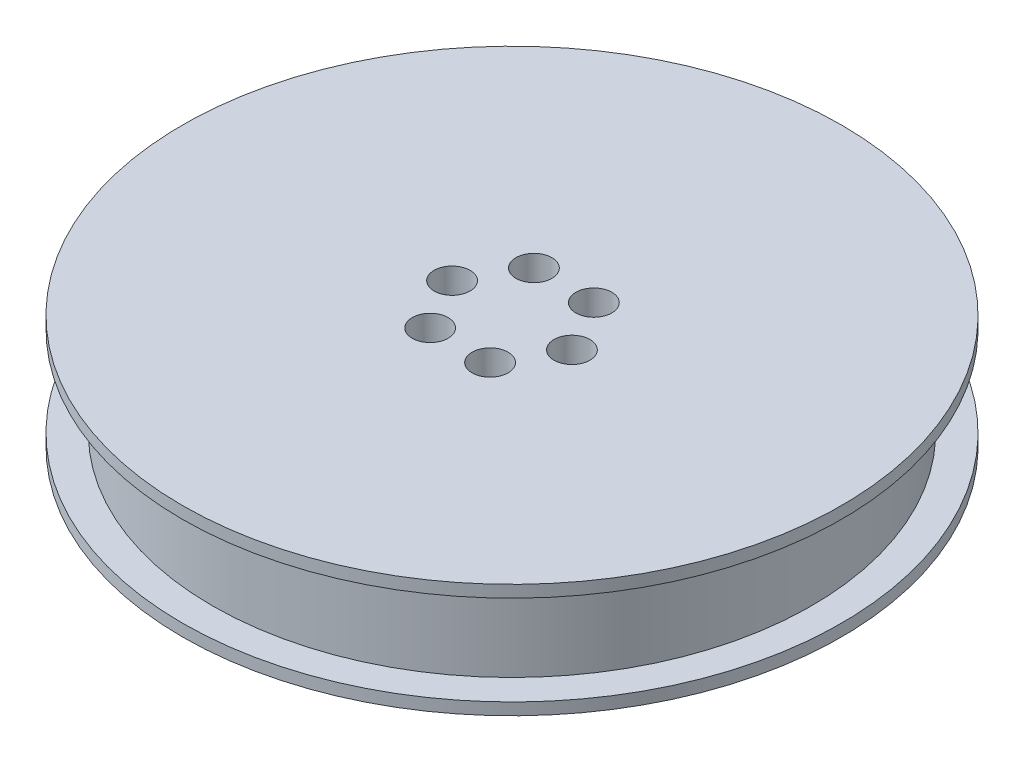
SolidWorks part; units mm, degrees
material "PETG"
ref_plane "Front Plane" through (0, 0, 0) normal (0, 0, 1) x (1, 0, 0)
ref_plane "Top Plane" through (0, 0, 0) normal (0, 1, 0) x (1, 0, 0)
ref_plane "Right Plane" through (0, 0, 0) normal (1, 0, 0) x (0, 0, -1)
sketch "Sketch1" plane through (0, 0, 0) normal (0, 1, 0) x (1, 0, 0)
  circle A0 centre (0, 0) radius 50
  dimension "D1" = 100
extrude "Boss-Extrude1" add sketch "Sketch1" along normal mid plane 15
sketch "Sketch2" plane through (0, 7.5, 0) normal (0, 1, 0) x (1, 0, 0)
  circle A0 centre (0, 0) radius 55
  dimension "D1" = 110
extrude "Boss-Extrude2" add sketch "Sketch2" along normal blind 2
mirror "Mirror1" about plane through (0, 0, 0) normal (0, 1, 0) of "Boss-Extrude2"
sketch "Sketch3" plane through (0, 9.5, 0) normal (0, 1, 0) x (1, 0, 0)
  line L0 (0, 0) -> (10, 0) construction
  circle A0 centre (10, 0) radius 1.7
  circle A1 centre (5, -8.6603) radius 1.7
  circle A2 centre (-5, -8.6603) radius 1.7
  circle A3 centre (-10, 0) radius 1.7
  circle A4 centre (-5, 8.6603) radius 1.7
  circle A5 centre (5, 8.6603) radius 1.7
  dimension "D1" = 10
  dimension "D2" = 3.4
  dimension "D3" = 6
extrude "Cut-Extrude1" cut sketch "Sketch3" against normal through all
sketch "Sketch4" plane through (0, 9.5, 0) normal (0, 1, 0) x (1, 0, 0)
  line L0 (0, 0) -> (5, -8.6603) construction
  circle A0 centre (5, -8.6603) radius 3
  circle A1 centre (-5, -8.6603) radius 3
  circle A2 centre (-10, 0) radius 3
  circle A3 centre (-5, 8.6603) radius 3
  circle A4 centre (5, 8.6603) radius 3
  circle A5 centre (10, 0) radius 3
  dimension "D1" = 6
  dimension "D2" = 6
extrude "Cut-Extrude2" cut sketch "Sketch4" against normal blind 5
equation "\"pitch_dia\"= 100mm"
equation "\"D1@Sketch1\"=\"pitch_dia\""
equation "\"D1@Sketch2\"=\"pitch_dia\"+10.00mm"
